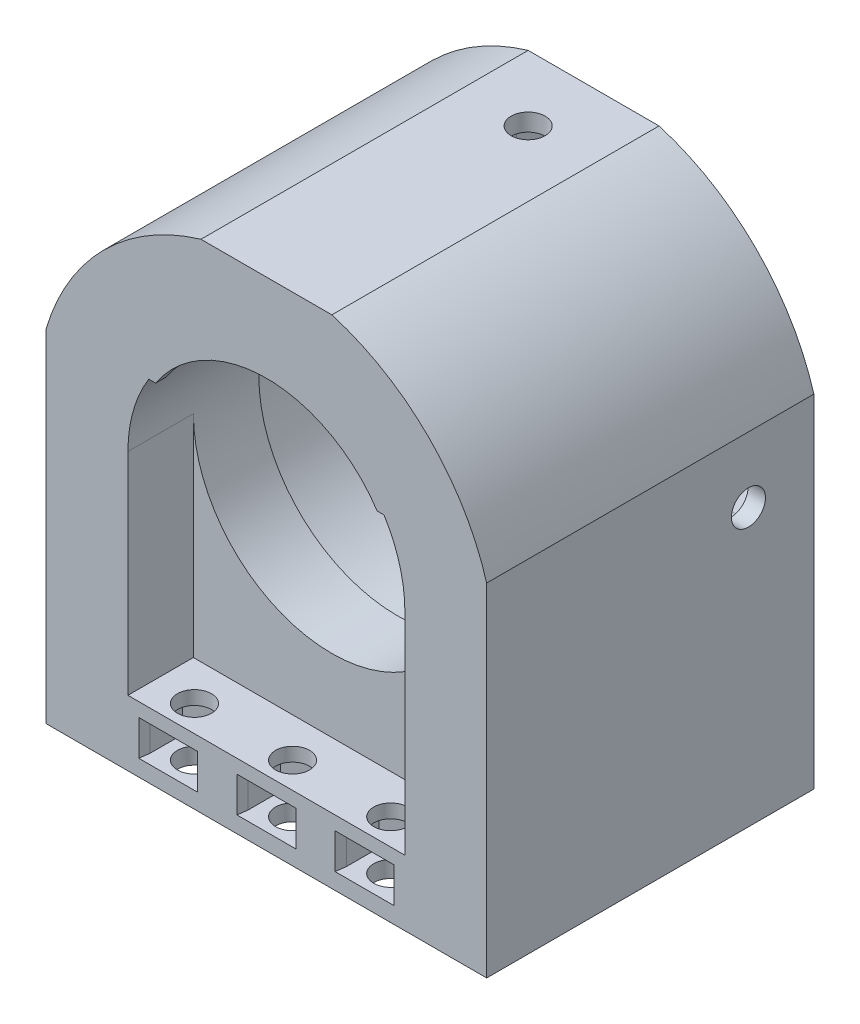
SolidWorks part; units mm, degrees
ref_plane "Front Plane" through (0, 0, 0) normal (0, 0, 1) x (1, 0, 0)
ref_plane "Top Plane" through (0, 0, 0) normal (0, 1, 0) x (1, 0, 0)
ref_plane "Right Plane" through (0, 0, 0) normal (1, 0, 0) x (0, 0, -1)
sketch "Sketch2" plane through (0, 0, 0) normal (0, 1, 0) x (1, 0, 0)
  line L0 (0, 0) -> (25.75, 0) construction
  line L1 (25.75, 0) -> (25.75, 2.14)
  line L2 (25.75, 2.14) -> (26.875, 5.32)
  line L3 (26.875, 5.32) -> (26.875, 25.4)
  line L4 (39.575, 25.4) -> (39.575, 0)
  line L5 (39.575, 0) -> (25.75, 0)
  line L6 (26.875, 25.4) -> (39.575, 25.4)
  line L7 (0, 0) -> (0, 46.1774) construction
  dimension "D1" = 25.75
  dimension "D2" = 26.875
  dimension "D3" = 5.32
  dimension "D4" = 3.18
  dimension "D5" = 12.7
  dimension "D6" = 25.4
revolve "Revolve1" add sketch "Sketch2" angle 360 about L7
sketch "Sketch3" plane through (0, 0, 0) normal (0, 0, 1) x (1, 0, 0)
  line L0 (26.875, 0) -> (39.575, 0)
  line L1 (-39.575, 0) -> (-26.875, 0)
  line L2 (-39.575, 0) -> (-39.575, -53.69)
  line L3 (-39.575, -53.69) -> (39.575, -53.69)
  line L4 (39.575, 0) -> (39.575, -53.69)
  line L6 (-26.875, 0) -> (-26.875, -40.99)
  line L7 (-26.875, -40.99) -> (26.875, -40.99)
  line L8 (26.875, 0) -> (26.875, -40.99)
  circle A0 centre (0, 0) radius 39.575 construction
  circle A2 centre (0, 0) radius 25.75 construction
  point P12 (0, -25.75)
  dimension "D1" = 12.7
  dimension "D2" = 12.7
  dimension "D3" = 12.7
  dimension "D4" = 15.24
extrude "Boss-Extrude2" add sketch "Sketch3" against normal blind 12.7
sketch "Sketch5" plane through (0, 0, 0) normal (0, 0, 1) x (1, 0, 0)
  line L1 (26.875, -40.99) -> (-26.875, -40.99)
  line L2 (26.875, -40.99) -> (26.875, 0)
  line L3 (26.875, 0) -> (-26.875, 0)
  line L4 (-26.875, -40.99) -> (-26.875, 0)
  line L6 (-26.875, -40.99) -> (-26.875, -29.0502) construction
  line L7 (26.875, -29.0502) -> (26.875, -40.99) construction
  line L8 (26.875, -40.99) -> (-26.875, -40.99) construction
extrude "Cut-Extrude1" cut sketch "Sketch5" against normal blind 12.7
sketch "Sketch6" plane through (0, 0, 0) normal (0, 0, 1) x (1, 0, 0)
  line L0 (-22.8328, 14.175) -> (22.8328, 14.175)
  arc A0 (-22.8328, 14.175) -> (22.8328, 14.175) centre (0, 0) ccw
  point P6 (0, 26.875)
  dimension "D1" = 12.7
extrude "Cut-Extrude2" cut sketch "Sketch6" against normal blind 12.7
sketch "Sketch7" plane through (0, -53.69, 0) normal (0, -1, 0) x (1, 0, 0)
  line L0 (-39.575, -12.7) -> (-39.575, 0) construction
  line L1 (39.575, -12.7) -> (-39.575, -12.7)
  line L2 (39.575, -12.7) -> (39.575, -25.4)
  line L3 (39.575, -25.4) -> (-39.575, -25.4)
  line L4 (-39.575, -12.7) -> (-39.575, -25.4)
  dimension "D1" = 12.7
extrude "Boss-Extrude3" add sketch "Sketch7" against normal up to surface (53.69 mm away) up to face at (39.575, 0, -25.4)
sketch "Sketch8" plane through (0, 0, 0) normal (0, 1, 0) x (1, 0, 0)
  line L1 (-39.575, 25.4) -> (-39.575, 63.5)
  line L2 (-39.575, 63.5) -> (-29.845, 63.5)
  line L3 (-29.845, 63.5) -> (-29.845, 25.4)
  line L5 (39.575, 25.4) -> (-39.575, 25.4) construction
  line L6 (-29.845, 25.4) -> (-39.575, 25.4)
  line L7 (0, 0) -> (0, 125.228) construction
  line L8 (-39.575, 0) -> (39.575, 0) construction
  dimension "D3" = 29.845
  dimension "D5" = 38.1
revolve "Revolve2" add sketch "Sketch8" angle 360 about L7
sketch "Sketch9" plane through (0, 0, 0) normal (0, 1, 0) x (1, 0, 0)
  circle A0 centre (0, 5.08) radius 3.302
  circle A1 centre (19.05, 5.08) radius 3.302
  circle A2 centre (-19.05, 5.08) radius 3.302
  dimension "D1" = 6.604
  dimension "D2" = 5.08
  dimension "D3" = 19.05
  dimension "D4" = 19.05
extrude "Cut-Extrude3" cut sketch "Sketch9" against normal through all
sketch "Sketch10" plane through (0, -53.69, 0) normal (0, -1, 0) x (-1, 0, 0)
  line L0 (-24.511, 1.9271) -> (-24.765, 0)
  line L1 (-19.05, 11.3858) -> (-24.511, 8.2329)
  line L2 (-24.511, 8.2329) -> (-24.511, 1.9271)
  line L3 (-24.511, 1.9271) -> (-19.05, -1.2258) construction
  line L4 (-19.05, -1.2258) -> (-13.589, 1.9271) construction
  line L5 (-13.589, 1.9271) -> (-13.589, 8.2329)
  line L6 (-13.589, 8.2329) -> (-19.05, 11.3858)
  line L7 (0, 11.3858) -> (-5.461, 8.2329)
  line L8 (-5.461, 8.2329) -> (-5.461, 1.9271)
  line L9 (-5.461, 1.9271) -> (0, -1.2258) construction
  line L10 (0, -1.2258) -> (5.461, 1.9271) construction
  line L11 (5.461, 1.9271) -> (5.461, 8.2329)
  line L12 (5.461, 8.2329) -> (0, 11.3858)
  line L13 (19.05, 11.3858) -> (13.589, 8.2329)
  line L14 (13.589, 8.2329) -> (13.589, 1.9271)
  line L15 (13.589, 1.9271) -> (19.05, -1.2258) construction
  line L16 (19.05, -1.2258) -> (24.511, 1.9271) construction
  line L17 (24.511, 1.9271) -> (24.511, 8.2329)
  line L18 (24.511, 8.2329) -> (19.05, 11.3858)
  line L19 (39.575, 0) -> (-39.575, 0) construction
  line L20 (-24.765, 0) -> (-13.335, 0)
  line L21 (-13.335, 0) -> (-13.589, 1.9271)
  line L22 (-5.461, 1.9271) -> (-5.715, 0)
  line L23 (-5.715, 0) -> (5.715, 0)
  line L24 (5.715, 0) -> (5.461, 1.9271)
  line L25 (13.589, 1.9271) -> (13.335, 0)
  line L26 (13.335, 0) -> (24.765, 0)
  line L27 (24.765, 0) -> (24.511, 1.9271)
  circle A0 centre (-19.05, 5.08) radius 5.461 construction
  circle A1 centre (0, 5.08) radius 5.461 construction
  circle A2 centre (19.05, 5.08) radius 5.461 construction
  point P19 (-19.05, 0)
  point P32 (19.05, 0)
  point P35 (0, 0)
  dimension "D1" = 10.922
  dimension "D2" = 10.922
  dimension "D3" = 10.922
  dimension "D4" = 11.43
  dimension "D5" = 11.43
  dimension "D6" = 11.43
extrude "Cut-Extrude4" cut sketch "Sketch10" against normal blind 6.858 from offset 3.175 offset against normal yes
sketch "Sketch15" plane through (0, 0, -25.4) normal (0, 0, -1) x (-1, 0, 0)
  line L5 (39.575, -53.69) -> (39.575, 0)
  line L8 (-39.575, 0) -> (-39.575, -53.69)
  line L9 (-39.575, -53.69) -> (39.575, -53.69)
  line L10 (39.575, -53.69) -> (39.575, 0)
  line L13 (-39.575, 0) -> (-39.575, -53.69)
  line L14 (-39.575, -53.69) -> (39.575, -53.69)
  arc A1 (-39.575, 0) -> (39.575, 0) centre (0, 0) ccw
  arc A2 (-39.575, 0) -> (39.575, 0) centre (0, 0) ccw
  dimension "D1" = 0
extrude "Boss-Extrude6" add sketch "Sketch15" along normal up to surface (38.1 mm away) up to face at (39.575, 0, -63.5)
sketch "Sketch12" plane through (0, 0, -63.5) normal (0, 0, -1) x (-1, 0, 0)
  line L1 (-12.7, 42.75) -> (12.7, 42.75)
  line L2 (-12.7, 42.75) -> (-12.7, 36.4)
  line L3 (-12.7, 36.4) -> (12.7, 36.4)
  line L4 (12.7, 42.75) -> (12.7, 36.4)
  line L5 (-12.7, 42.75) -> (12.7, 36.4) construction
  line L6 (-12.7, 36.4) -> (12.7, 42.75) construction
  circle A0 centre (0, 0) radius 39.575 construction
  point P0 (0, 39.575)
  dimension "D1" = 6.35
  dimension "D2" = 25.4
extrude "Boss-Extrude4" add sketch "Sketch12" against normal blind 25.4
sketch "Sketch11" plane through (0, 0, 0) normal (0, 1, 0) x (1, 0, 0)
  line L0 (29.845, 63.5) -> (-29.845, 63.5) construction
  line L1 (0, 44.4942) -> (5.461, 47.6471)
  line L2 (5.461, 47.6471) -> (5.461, 53.9529)
  line L3 (5.461, 53.9529) -> (0, 57.1058) construction
  line L4 (0, 57.1058) -> (-5.461, 53.9529) construction
  line L5 (-5.461, 53.9529) -> (-5.461, 47.6471)
  line L6 (-5.461, 47.6471) -> (0, 44.4942)
  line L7 (-5.461, 53.9529) -> (-5.715, 63.5)
  line L8 (39.575, 63.5) -> (-39.575, 63.5) construction
  line L9 (-5.715, 63.5) -> (5.715, 63.5)
  line L10 (5.715, 63.5) -> (5.461, 53.9529)
  circle A0 centre (0, 50.8) radius 5.461 construction
  point P19 (0, 63.5)
  dimension "D1" = 10.922
  dimension "D2" = 12.7
  dimension "D3" = 11.43
extrude "Cut-Extrude5" cut sketch "Sketch11" against normal blind 6.858 from offset 39.37
ref_axis "Axis1" through (0, 0, -66.675) along (0, 0, 1)
sketch "Sketch13" plane through (0, 0, 0) normal (0, 1, 0) x (1, 0, 0)
  line L0 (0, 66.675) -> (0, -3.175) construction
  line L1 (-12.7, 63.5) -> (12.7, 63.5) construction
  circle A0 centre (0, 50.8) radius 3.302
  dimension "D1" = 6.604
  dimension "D2" = 12.7
extrude "Cut-Extrude6" cut sketch "Sketch13" along normal through all
pattern_circular "CirPattern1" count 4 over 360 about axis through (0, 0, -66.675) along (0, 0, 1) of "Boss-Extrude4", "Cut-Extrude5", "Cut-Extrude6"
sketch "Sketch14" plane through (0, 0, -38.1) normal (0, 0, 1) x (1, 0, 0)
  line L3 (39.575, -12.7) -> (42.75, -12.7)
  line L4 (42.75, -12.7) -> (42.75, 12.7)
  line L5 (42.75, 12.7) -> (37.4819, 12.7)
  line L6 (39.575, -12.7) -> (42.75, -12.7)
  line L7 (42.75, -12.7) -> (42.75, 12.7)
  line L8 (42.75, 12.7) -> (37.4819, 12.7)
  line L9 (12.7, 37.4819) -> (12.7, 42.75)
  line L10 (12.7, 42.75) -> (-12.7, 42.75)
  line L11 (-12.7, 42.75) -> (-12.7, 37.4819)
  line L12 (12.7, 37.4819) -> (12.7, 42.75)
  line L13 (12.7, 42.75) -> (-12.7, 42.75)
  line L14 (-12.7, 42.75) -> (-12.7, 37.4819)
  line L15 (-37.4819, 12.7) -> (-42.75, 12.7)
  line L16 (-42.75, 12.7) -> (-42.75, -12.7)
  line L17 (-42.75, -12.7) -> (-39.575, -12.7)
  line L18 (-37.4819, 12.7) -> (-42.75, 12.7)
  line L19 (-42.75, 12.7) -> (-42.75, -12.7)
  line L20 (-42.75, -12.7) -> (-39.575, -12.7)
  line L22 (39.575, 0) -> (39.575, -12.7)
  line L23 (39.575, 0) -> (39.575, -12.7)
  line L24 (-39.575, -12.7) -> (-39.575, 0)
  line L25 (-39.575, -12.7) -> (-39.575, 0)
  arc A1 (39.575, 0) -> (37.4819, 12.7) centre (0, 0) ccw
  arc A2 (39.575, 0) -> (37.4819, 12.7) centre (0, 0) ccw
  arc A3 (12.7, 37.4819) -> (-12.7, 37.4819) centre (0, 0) ccw
  arc A4 (12.7, 37.4819) -> (-12.7, 37.4819) centre (0, 0) ccw
  arc A5 (-37.4819, 12.7) -> (-39.575, 0) centre (0, 0) ccw
  arc A6 (-37.4819, 12.7) -> (-39.575, 0) centre (0, 0) ccw
  dimension "D1" = 0
  dimension "D2" = 0
  dimension "D3" = 0
extrude "Boss-Extrude5" add sketch "Sketch14" along normal up to surface (38.1 mm away)
sketch "Sketch16" plane through (0, 0, -63.5) normal (0, 0, -1) x (-1, 0, 0)
  line L1 (42.75, -12.7) -> (39.575, -12.7)
  line L2 (42.75, -12.7) -> (42.75, -53.69)
  line L3 (42.75, -53.69) -> (39.575, -53.69)
  line L4 (39.575, -12.7) -> (39.575, -53.69)
  line L5 (-42.75, -12.7) -> (-39.575, -12.7)
  line L6 (-42.75, -12.7) -> (-42.75, -53.69)
  line L7 (-42.75, -53.69) -> (-39.575, -53.69)
  line L8 (-39.575, -12.7) -> (-39.575, -53.69)
extrude "Boss-Extrude7" add sketch "Sketch16" against normal up to surface (63.5 mm away)
sketch "Sketch17" plane through (0, 0, -63.5) normal (0, 0, -1) x (-1, 0, 0)
  line L0 (-42.75, 12.7) -> (-37.4819, 12.7)
  line L1 (37.4819, 12.7) -> (42.75, 12.7)
  line L2 (-12.7, 42.75) -> (-12.7, 37.4819)
  line L3 (12.7, 42.75) -> (12.7, 37.4819)
  arc A0 (42.75, 12.7) -> (12.7, 42.75) centre (0, 0) ccw
  arc A1 (37.4819, 12.7) -> (12.7, 37.4819) centre (0, 0) ccw
  arc A2 (-12.7, 42.75) -> (-42.75, 12.7) centre (0, 0) ccw
  arc A3 (-12.7, 37.4819) -> (-37.4819, 12.7) centre (0, 0) ccw
extrude "Boss-Extrude9" add sketch "Sketch17" against normal up to surface (63.5 mm away)
